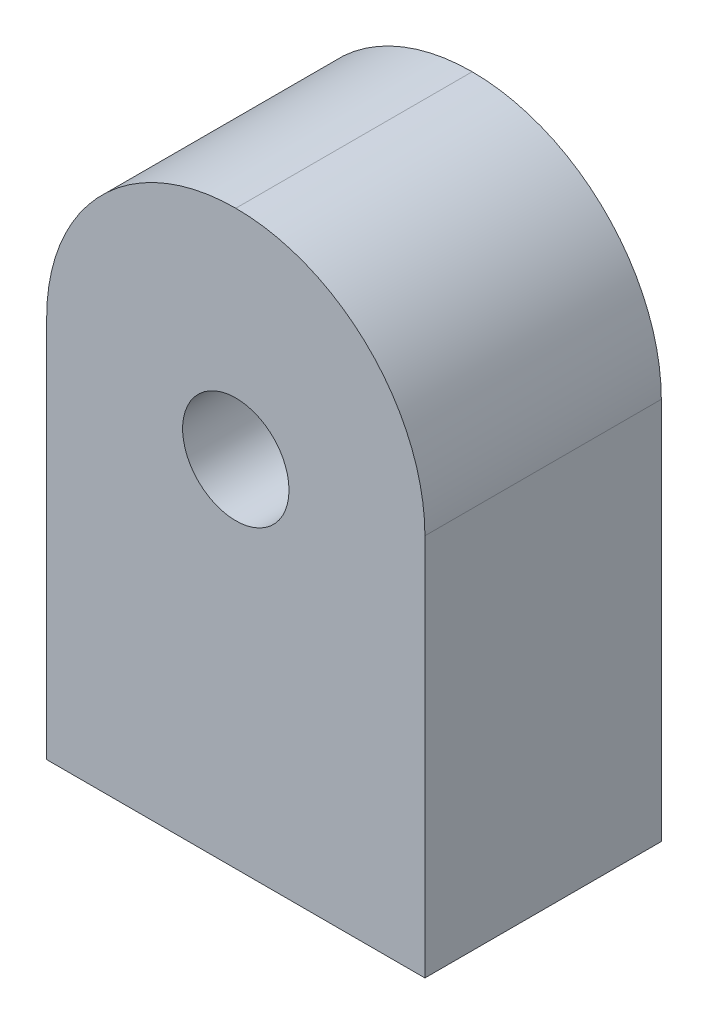
SolidWorks part; units mm, degrees
ref_plane "Front Plane" through (0, 0, 0) normal (0, 0, 1) x (1, 0, 0)
ref_plane "Top Plane" through (0, 0, 0) normal (0, 1, 0) x (1, 0, 0)
ref_plane "Right Plane" through (0, 0, 0) normal (1, 0, 0) x (0, 0, -1)
sketch "Sketch1" plane through (0, 0, 0) normal (0, 0, 1) x (1, 0, 0)
  line L1 (0, 0) -> (16, 0)
  line L2 (0, 0) -> (0, 20)
  line L3 (0, 20) -> (16, 20)
  line L4 (16, 0) -> (16, 20)
  dimension "D1" = 16
  dimension "D2" = 20
extrude "Boss-Extrude1" add sketch "Sketch1" along normal blind 10
sketch "Sketch2" plane through (0, 0, 10) normal (0, 0, 1) x (1, 0, 0)
  line L0 (8, 0) -> (8, 20) construction
  line L1 (0, 0) -> (16, 0) construction
  line L2 (16, 20) -> (0, 20) construction
  circle A0 centre (8, 10.8) radius 2.25
  dimension "D1" = 4.5
  dimension "D2" = 10.8
extrude "Cut-Extrude1" cut sketch "Sketch2" against normal through all
fillet "Fillet1" radius 8 2 edges at (16, 20, 5) (0, 20, 5)
sketch "Sketch3" plane through (0, 0, 10) normal (0, 0, 1) x (1, 0, 0)
  line L1 (0, 0) -> (16, 0)
  line L2 (0, 0) -> (0, -4.2)
  line L3 (0, -4.2) -> (16, -4.2)
  line L4 (16, 0) -> (16, -4.2)
  dimension "D1" = 4.2
extrude "Boss-Extrude2" add sketch "Sketch3" against normal blind 10
